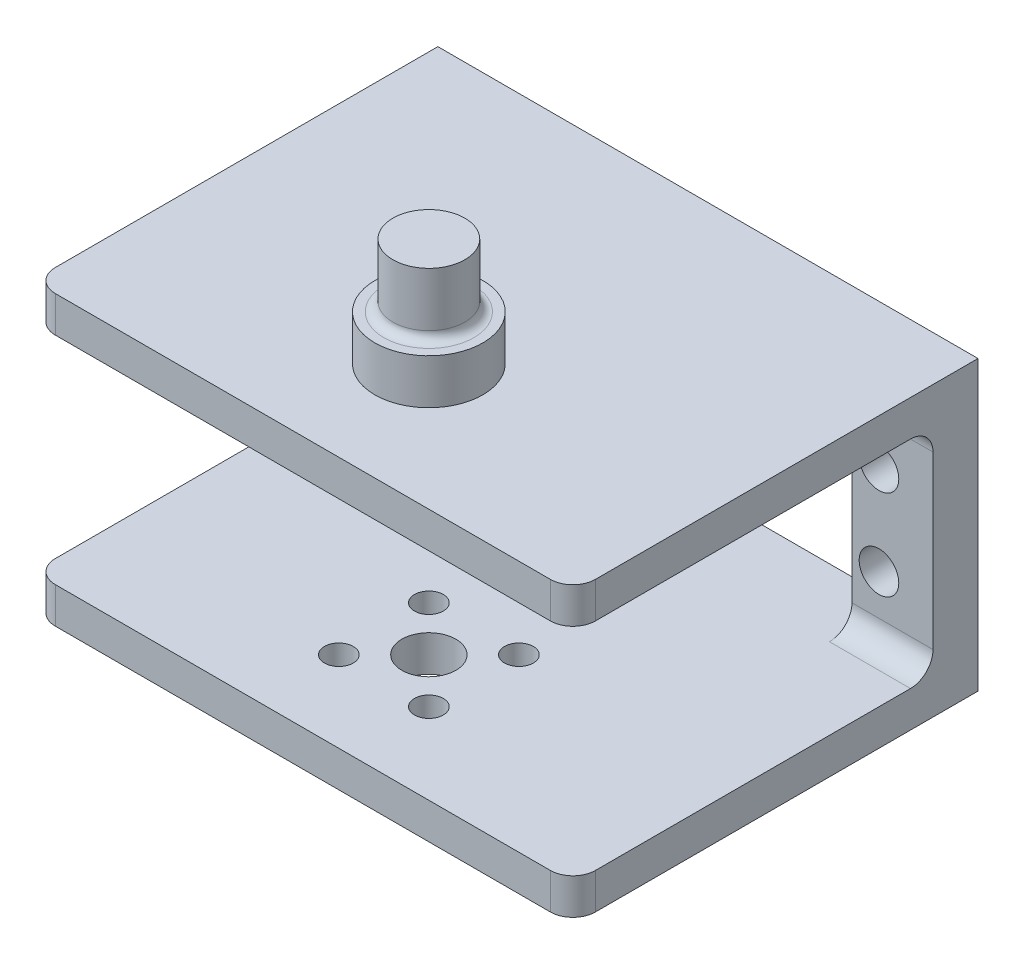
SolidWorks part; units mm, degrees
ref_plane "Front Plane" through (0, 0, 0) normal (0, 0, 1) x (1, 0, 0)
ref_plane "Top Plane" through (0, 0, 0) normal (0, 1, 0) x (1, 0, 0)
ref_plane "Right Plane" through (0, 0, 0) normal (1, 0, 0) x (0, 0, -1)
sketch "Sketch1" plane through (0, 0, 0) normal (0, 0, 1) x (1, 0, 0)
  line L0 (-82.0256, 30) -> (-82.0256, -25.5559) construction
  line L2 (-112.0256, 7.6852) -> (-112.0256, 27.1852)
  line L4 (-103.0256, 7.6852) -> (-103.0256, 27.1852)
  line L9 (-112.0256, 27.1852) -> (-112.0256, 31.6852)
  line L10 (-112.0256, 7.6852) -> (-52.0256, 7.6852)
  line L11 (-112.0256, 7.6852) -> (-112.0256, 3.6852)
  line L12 (-112.0256, 3.6852) -> (-52.0256, 3.6852)
  line L13 (-52.0256, 7.6852) -> (-52.0256, 3.6852)
  line L14 (-112.0256, 31.6852) -> (-103.0256, 31.6852)
  line L15 (-103.0256, 31.6852) -> (-103.0256, 27.1852)
  line L16 (-52.0256, 27.1852) -> (-52.0256, 31.6852)
  line L17 (-112.0256, 31.6852) -> (-52.0256, 31.6852)
  line L18 (-112.0256, 31.6852) -> (-112.0256, 35.6852)
  line L19 (-112.0256, 35.6852) -> (-52.0256, 35.6852)
  line L20 (-52.0256, 31.6852) -> (-52.0256, 35.6852)
  line L21 (-61.0256, 31.6852) -> (-61.0256, 27.1852)
  line L22 (-61.0256, 7.6852) -> (-61.0256, 27.1852)
  line L23 (-52.0256, 7.6852) -> (-52.0256, 27.1852)
  circle A0 centre (-106.0256, 24.6852) radius 2.2
  circle A1 centre (-106.0256, 14.6852) radius 2.2
  circle A2 centre (-58.0256, 14.6852) radius 2.2
  circle A3 centre (-58.0256, 24.6852) radius 2.2
  point P29 (-103.0256, 29.6852)
  point P32 (-112.0256, 29.6852)
  dimension "D3" = 4.4
  dimension "D4" = 4.4
  dimension "D12" = 3
  dimension "D1" = 22
  dimension "D2" = 4
  dimension "D5" = 10
  dimension "D6" = 7
  dimension "D7" = 60
  dimension "D8" = 42
  dimension "D9" = 4
  dimension "D10" = 55.5559
  dimension "D11" = 3
  dimension "D13" = 7
extrude "Boss-Extrude1" add sketch "Sketch1" along normal blind 45 contours L10 L0 L12 L13 | L0 L10 L11 L12 region at (-67.0256, 5.6852, 0) region at (-97.0256, 5.6852, 0)
extrude "Boss-Extrude2" add sketch "Sketch1<3>" along normal blind 5 contours L2 L10 L4 A1 A0 | L10 L23 L16 L17 L21 L22 A2 A3 region at (-107.7714, 19.6852, 0) region at (-56.2799, 19.6852, 0)
sketch "Sketch1<3>" plane through (0, 0, 0) normal (0, 0, 1) x (1, 0, 0) same geometry as "Sketch1"
sketch "Sketch2" plane through (0, 7.6852, 0) normal (0, 1, 0) x (1, 0, 0)
  line L0 (-82.0256, -6.4694) -> (-82.0256, -26.5346) construction
  line L1 (-96.5112, -31) -> (-67.862, -31) construction
  line L2 (-52.0256, -45) -> (-52.0256, -5) construction
  line L3 (-112.0256, -45) -> (-52.0256, -45) construction
  circle A0 centre (-82.0256, -31) radius 3
  circle A1 centre (-77.0256, -26) radius 1.6
  circle A2 centre (-87.0256, -26) radius 1.6
  circle A3 centre (-77.0256, -36) radius 1.6
  circle A4 centre (-87.0256, -36) radius 1.6
  dimension "D1" = 6
  dimension "D2" = 3.2
  dimension "D3" = 3.2
  dimension "D4" = 5
  dimension "D5" = 5
  dimension "D6" = 10
  dimension "D7" = 5
  dimension "D8" = 30
  dimension "D9" = 28.6493
  dimension "D10" = 14
extrude "Cut-Extrude1" cut sketch "Sketch2" against normal through all
extrude "Boss-Extrude3" add sketch "Sketch1<4>" along normal blind 45 contours L17 L20 L19 L18 L14 region at (-82.0256, 33.6852, 0)
sketch "Sketch1<4>" plane through (0, 0, 0) normal (0, 0, 1) x (1, 0, 0) same geometry as "Sketch1"
fillet "Fillet1" radius 2.5 4 edges at (-52.0256, 5.6852, 45) (-112.0256, 5.6852, 45) (-52.0256, 33.6852, 45) (-112.0256, 33.6852, 45)
fillet "Fillet3" radius 2.5 4 edges at (-107.5256, 7.6852, 5) (-56.5256, 7.6852, 5) (-56.5256, 31.6852, 5) (-107.5256, 31.6852, 5)
sketch "Sketch3" plane through (0, 35.6852, 0) normal (0, 1, 0) x (1, 0, 0)
  line L0 (-52.0256, -42.5) -> (-52.0256, 0) construction
  line L3 (-109.5256, -45) -> (-54.5256, -45) construction
  circle A0 centre (-82.0256, -31) radius 4
  dimension "D3" = 8
  dimension "D1" = 30
  dimension "D2" = 14
extrude "Boss-Extrude4" add sketch "Sketch3" along normal blind 12
sketch "Sketch4" plane through (0, 35.6852, 0) normal (0, 1, 0) x (1, 0, 0)
  circle A0 centre (-82.0256, -31) radius 6
  circle A1 centre (-82.0256, -31) radius 4 construction
  dimension "D1" = 2
extrude "Boss-Extrude5" add sketch "Sketch4" along normal blind 5
fillet "Fillet4" radius 1 1 edges at (-82.0256, 40.6852, 35)
